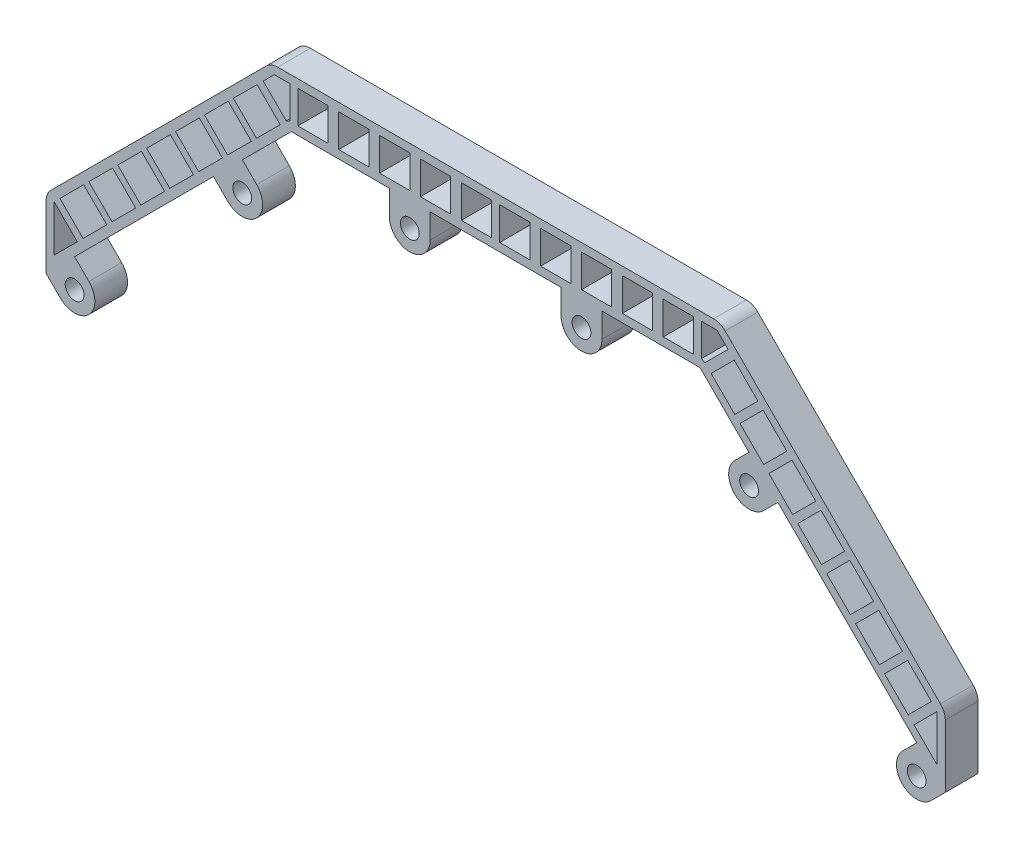
SolidWorks part; units mm, degrees
ref_plane "Front Plane" through (0, 0, 0) normal (0, 0, 1) x (1, 0, 0)
ref_plane "Top Plane" through (0, 0, 0) normal (0, 1, 0) x (1, 0, 0)
ref_plane "Right Plane" through (0, 0, 0) normal (1, 0, 0) x (0, 0, -1)
sketch "Sketch2" plane through (0, 0, 0) normal (0, 0, 1) x (1, 0, 0)
  line L0 (-55, 25) -> (-55, -25) construction
  line L1 (-55, -25) -> (-25, -55) construction
  line L2 (-25, -55) -> (25, -55) construction
  line L3 (25, -55) -> (55, -25) construction
  line L4 (55, -25) -> (55, 25) construction
  line L5 (55, 25) -> (25, 55) construction
  line L6 (25, 55) -> (-25, 55) construction
  line L7 (-25, 55) -> (-55, 25) construction
  point P7 (0, 55)
  point P9 (-55, 0)
  point P10 (0, 0)
  point P12 (0, 0)
  dimension "D1" = 50
  dimension "D2" = 30
  dimension "D3" = 30
  dimension "D4" = 30
sketch "Sketch3" plane through (0, 0, 0) normal (0, 0, 1) x (1, 0, 0)
  line L0 (-55, 25) -> (-53.25, 23.25)
  line L1 (-49.75, 26.75) -> (-51.5, 28.5)
  line L2 (-25, 55) -> (-55, 25) construction
  line L3 (-51.5, 28.5) -> (-34.5178, 45.4822)
  line L4 (-25, 55) -> (-13, 55)
  line L5 (25, 55) -> (-25, 55) construction
  line L6 (-13, 55) -> (-13, 52)
  line L7 (-8, 52) -> (-8, 55)
  line L8 (-8, 55) -> (0, 55)
  line L9 (0, 55) -> (0, 61)
  line L10 (0, 61) -> (-27.4853, 61)
  line L11 (-27.4853, 61) -> (-55, 33.4853)
  line L12 (-55, 33.4853) -> (-55, 25)
  line L13 (-34.5178, 45.4822) -> (-32.7678, 43.7322)
  line L14 (-29.2322, 47.2678) -> (-30.9822, 49.0178)
  line L15 (-30.9822, 49.0178) -> (-25, 55)
  arc A0 (-53.25, 23.25) -> (-49.75, 26.75) centre (-51.5, 25) ccw
  arc A1 (-13, 52) -> (-8, 52) centre (-10.5, 52) ccw
  arc A2 (-32.7678, 43.7322) -> (-29.2322, 47.2678) centre (-31, 45.5) ccw
  circle A3 centre (-10.5, 52) radius 1.15
  circle A4 centre (-31, 45.5) radius 1.15
  circle A5 centre (-51.5, 25) radius 1.15
  dimension "D2" = 2.5
  dimension "D8" = 2.5
  dimension "D10" = 2.4749
  dimension "D11" = 2.3
  dimension "D4" = 6
  dimension "D5" = 6
  dimension "D6" = 3
  dimension "D3" = 12
  dimension "D9" = 6
  dimension "D1" = 9.5
  dimension "D7" = 3.5
extrude "Boss-Extrude1" add sketch "Sketch3" along normal mid plane 4
fillet "Fillet1" radius 2 2 edges at (-55, 33.4853, 0) (-27.4853, 61, 0)
sketch "Sketch5" plane through (0, 0, 2) normal (0, 0, 1) x (1, 0, 0)
  line L0 (-28.4283, 58.6428) -> (-27.0711, 60)
  line L1 (-27.0711, 60) -> (-25.1517, 60)
  line L2 (-25.1517, 60) -> (-25.1517, 56.0196)
  line L3 (-25.1517, 56.0196) -> (-25.6137, 55.8282)
  line L4 (-25.6137, 55.8282) -> (-28.4283, 58.6428)
  line L5 (-54, 33.0711) -> (-54, 27.4142)
  line L6 (-54, 27.4142) -> (-51.1716, 30.2426)
  line L7 (-51.1716, 30.2426) -> (-54, 33.0711)
  line L8 (-25, 55) -> (-55, 25) construction
  line L9 (25, 55) -> (-25, 55) construction
  line L10 (0, 61) -> (-26.6569, 61) construction
  line L11 (-28.0711, 60.4142) -> (-54.4142, 34.0711) construction
  line L12 (-55, 32.6569) -> (-55, 25) construction
  circle A0 centre (-25, 55) radius 1 construction
  dimension "D1" = 2
  dimension "D2" = 1
  dimension "D3" = 1
  dimension "D4" = 0.5
  dimension "D5" = 1
  dimension "D6" = 1
  dimension "D7" = 1
extrude "Cut-Extrude1" cut sketch "Sketch5" against normal through all
sketch "Sketch6" plane through (0, 0, 0) normal (0, 0, 1) x (1, 0, 0)
  line L0 (-53.2929, 33.7782) -> (-50.3938, 36.6773)
  line L1 (-50.3938, 36.6773) -> (-47.5653, 33.8489)
  line L2 (-47.5653, 33.8489) -> (-50.4645, 30.9497)
  line L3 (-50.4645, 30.9497) -> (-53.2929, 33.7782)
  line L4 (-25, 55) -> (-55, 25) construction
  line L5 (-28.0711, 60.4142) -> (-54.4142, 34.0711) construction
  line L7 (-51.1716, 30.2426) -> (-54, 33.0711) construction
  dimension "D2" = 1
  dimension "D3" = 1
  dimension "D1" = 1
  dimension "D4" = 4.1
extrude "Cut-Extrude2" cut sketch "Sketch6" against normal through all both and the other way through all
pattern_linear "LPattern1" count 7 spacing 5 along (0.7071, 0.7071, 0) of "Cut-Extrude2"
sketch "Sketch7" plane through (0, 0, 0) normal (0, 0, 1) x (1, 0, 0)
  line L0 (0, 61) -> (-26.6569, 61) construction
  line L1 (-4.2, 60) -> (-0.5, 60)
  line L2 (-4.2, 60) -> (-4.2, 56)
  line L3 (-4.2, 56) -> (-0.5, 56)
  line L4 (-0.5, 60) -> (-0.5, 56)
  line L5 (-25, 55) -> (-13, 55) construction
  line L6 (0, 55) -> (0, 61) construction
  dimension "D2" = 1
  dimension "D4" = 0.5
  dimension "D1" = 1
  dimension "D3" = 3.7
extrude "Cut-Extrude3" cut sketch "Sketch7" against normal through all both and the other way through all
pattern_linear "LPattern2" count 5 spacing 5 along (-1, 0, 0) of "Cut-Extrude3"
mirror "Mirror1" about plane through (0, 55, 2) normal (-1, 0, 0) of "Fillet1", "Cut-Extrude1", "Cut-Extrude2", "LPattern1", "Cut-Extrude3", "LPattern2", "Boss-Extrude1"
equation "\"D5@Sketch3\"=\"D4@Sketch3\""
equation "\"D8@Sketch3\"=\"D2@Sketch3\""
equation "\"D3@Sketch5\"=\"ridge\""
equation "\"D1@Sketch5\"=2 * \"ridge\""
equation "\"ridge\"= 1"
equation "\"D2@Sketch5\"= \"ridge\""
equation "\"D5@Sketch5\"= \"ridge\""
equation "\"D6@Sketch5\"= \"ridge\""
equation "\"D7@Sketch5\"=\"ridge\""
equation "\"D1@Sketch6\"=\"ridge\""
equation "\"D2@Sketch6\"=\"ridge\""
equation "\"D1@Sketch7\"=\"ridge\""
equation "\"D2@Sketch7\"=\"ridge\""
